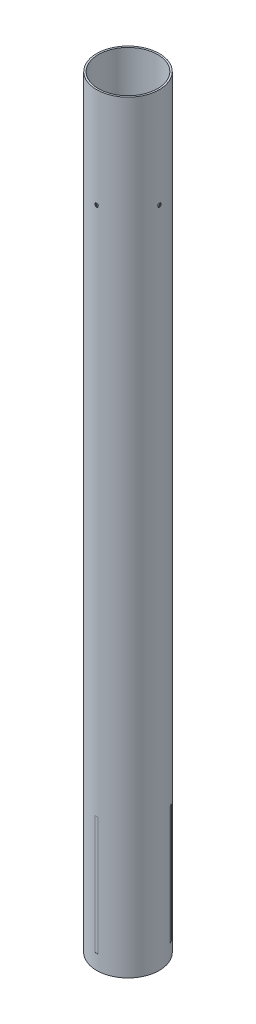
SolidWorks part; units mm, degrees
ref_plane "Front Plane" through (0, 0, 0) normal (0, 0, 1) x (1, 0, 0)
ref_plane "Top Plane" through (0, 0, 0) normal (0, 1, 0) x (1, 0, 0)
ref_plane "Right Plane" through (0, 0, 0) normal (1, 0, 0) x (0, 0, -1)
sketch "Sketch1" plane through (0, 0, 0) normal (0, 1, 0) x (1, 0, 0)
  circle A0 centre (0, 0) radius 53.721
  circle A1 centre (0, 0) radius 50.8
  dimension "D1" = 107.442
  dimension "D2" = 101.6
extrude "Tube Extrusion" add sketch "Sketch1" along normal blind 1308.1
ref_plane "Plane1" through (0, 0, 53.721) normal (0, 0, 1) x (1, 0, 0)
sketch "Sketch2" plane through (0, 0, 53.721) normal (0, 0, 1) x (1, 0, 0)
  line L0 (0, 1308.1) -> (0, 0) construction
  line L3 (53.721, 1308.1) -> (-53.721, 1308.1) construction
  circle A0 centre (0, 1136.65) radius 1.6383
  dimension "D1" = 3.2766
  dimension "D2" = 1136.65
extrude "Engine Block Hole" cut sketch "Sketch2" against normal up to next
pattern_circular "CirPattern1" count 4 over 360 about axis through (0, 1308.1, 0) along (0, -1, 0) of "Engine Block Hole"
sketch "Sketch3" plane through (0, 0, 53.721) normal (0, 0, 1) x (1, 0, 0)
  line L0 (0, 0) -> (0, 25.4) construction
  line L1 (-53.721, 0) -> (53.721, 0) construction
  line L3 (-2.667, 228.6) -> (2.667, 228.6)
  line L4 (-2.667, 228.6) -> (-2.667, 25.4)
  line L5 (-2.667, 25.4) -> (2.667, 25.4)
  line L6 (2.667, 228.6) -> (2.667, 25.4)
  point P8 (0, 25.4)
  dimension "D1" = 25.4
  dimension "D2" = 203.2
  dimension "D3" = 5.334
extrude "Fin Slots" cut sketch "Sketch3" against normal blind 0.254
pattern_circular "CirPattern2" count 3 over 360 about axis through (0, 1308.1, 0) along (0, -1, 0) of "Fin Slots"
sketch "Sketch4" plane through (0, 0, 53.721) normal (0, 0, 1) x (1, 0, 0)
  line L0 (0, 1308.1) -> (0, 0) construction
  line L1 (53.721, 1308.1) -> (-53.721, 1308.1) construction
  line L2 (-50.8, 0) -> (50.8, 0) construction
  circle A0 centre (0, 1136.65) radius 1.6383 construction
  circle A1 centre (0, 1136.65) radius 1.6383 construction
  circle A2 centre (0, 1136.65) radius 3.175
  dimension "D1" = 6.35
extrude "Cut-Extrude1" cut sketch "Sketch4" against normal blind 1.27
pattern_circular "CirPattern3" count 4 over 360 about axis through (0, 1308.1, 0) along (0, -1, 0) of "Cut-Extrude1"
